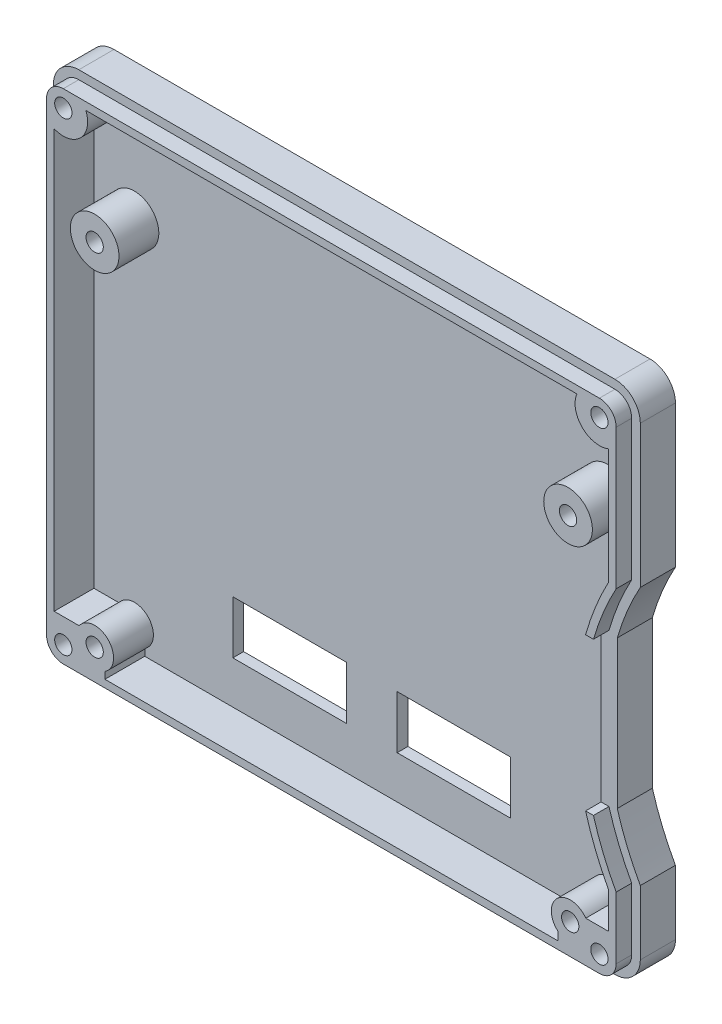
SolidWorks part; units mm, degrees
material "ABS"
ref_plane "Front Plane" through (0, 0, 0) normal (0, 0, 1) x (1, 0, 0)
ref_plane "Top Plane" through (0, 0, 0) normal (0, 1, 0) x (1, 0, 0)
ref_plane "Right Plane" through (0, 0, 0) normal (1, 0, 0) x (0, 0, -1)
sketch "Sketch1" plane through (0, 0, 0) normal (0, 0, 1) x (1, 0, 0)
  line L1 (-54.3, -47.7) -> (54.3, -47.7)
  line L2 (-54.3, -47.7) -> (-54.3, 47.7)
  line L3 (-54.3, 47.7) -> (54.3, 47.7)
  line L4 (54.3, -47.7) -> (54.3, 47.7)
  line L5 (-54.3, -47.7) -> (54.3, 47.7) construction
  line L6 (-54.3, 47.7) -> (54.3, -47.7) construction
  point P0 (0, 0)
  dimension "D1" = 108.6
  dimension "D2" = 95.4
extrude "Boss-Extrude1" add sketch "Sketch1" along normal blind 6.5
fillet "Fillet1" radius 4.7 4 edges at (-54.3, 47.7, 3.25) (-54.3, -47.7, 3.25) (54.3, -47.7, 3.25) (54.3, 47.7, 3.25)
sketch "Sketch4" plane through (0, 0, 6.5) normal (0, 0, 1) x (1, 0, 0)
  line L0 (54.3, -43) -> (54.3, 43) construction
  line L1 (-49.6, -47.7) -> (49.6, -47.7) construction
  line L2 (50.037, 6.4675) -> (50.037, -20.8702)
  arc A0 (50.037, -20.8702) -> (50.037, 6.4675) centre (97.196, -7.2014) ccw
  dimension "D1" = 98.2
  dimension "D2" = 42.896
  dimension "D3" = 40.4986
  dimension "D4" = 4.263
extrude "Cut-Extrude2" cut sketch "Sketch4" against normal through all
shell "Shell1" thickness 3 removed face at (17.3413, -2.4004, 6.5)
sketch "Sketch3" plane through (0, 0, 6.5) normal (0, 0, 1) x (1, 0, 0)
  line L0 (-49.6, -47.7) -> (49.6, -47.7) construction
  line L1 (-25.6, -27) -> (-4.6, -27)
  line L2 (-25.6, -27) -> (-25.6, -36.8)
  line L3 (-25.6, -36.8) -> (-4.6, -36.8)
  line L4 (-4.6, -27) -> (-4.6, -36.8)
  line L5 (4.8, -27) -> (25.8, -27)
  line L6 (4.8, -27) -> (4.8, -36.8)
  line L7 (4.8, -36.8) -> (25.8, -36.8)
  line L8 (25.8, -27) -> (25.8, -36.8)
  line L9 (-54.3, 43) -> (-54.3, -43) construction
  dimension "D1" = 21
  dimension "D2" = 9.4
  dimension "D3" = 9.8
  dimension "D4" = 10.9
  dimension "D5" = 28.7
extrude "Cut-Extrude1" cut sketch "Sketch3" against normal through all
sketch "Sketch5" plane through (0, 0, 6.5) normal (0, 0, 1) x (1, 0, 0)
  line L0 (-49.6, -47.7) -> (49.6, -47.7) construction
  line L1 (-54.3, 43) -> (-54.3, -43) construction
  line L2 (49.6, 47.7) -> (-49.6, 47.7) construction
  line L3 (54.3, 16.6888) -> (54.3, 43) construction
  line L4 (54.3, -43) -> (54.3, -31.0915) construction
  line L5 (-49.6, -47.7) -> (49.6, -47.7) construction
  line L6 (-54.3, 43) -> (-54.3, -43) construction
  line L7 (49.6, 47.7) -> (-49.6, 47.7) construction
  line L8 (54.3, 16.6888) -> (54.3, 43) construction
  line L9 (54.3, -43) -> (54.3, -31.0915) construction
  line L10 (52.7, 17.1008) -> (52.7, 43)
  line L11 (49.6, 46.1) -> (-49.6, 46.1)
  line L12 (-52.7, 43) -> (-52.7, -43)
  line L13 (-49.6, -46.1) -> (49.6, -46.1)
  line L14 (52.7, -43) -> (52.7, -31.5035)
  line L15 (-49.6, -44.7) -> (49.6, -44.7) construction
  line L16 (-51.3, 43) -> (-51.3, -43) construction
  line L17 (49.6, 44.7) -> (-49.6, 44.7) construction
  line L18 (51.3, 17.4556) -> (51.3, 43) construction
  line L19 (51.3, -43) -> (51.3, -31.8583) construction
  line L20 (-49.6, -44.7) -> (49.6, -44.7)
  line L21 (-51.3, 43) -> (-51.3, -43)
  line L22 (49.6, 44.7) -> (-49.6, 44.7)
  line L23 (51.3, 17.4556) -> (51.3, 43)
  line L24 (51.3, -43) -> (51.3, -31.8583)
  line L25 (48.5002, 6.9129) -> (47.0443, 6.9129)
  line L26 (48.5002, -21.3156) -> (47.0443, -21.3156)
  arc A0 (-54.3, -43) -> (-49.6, -47.7) centre (-49.6, -43) ccw construction
  arc A1 (-49.6, 47.7) -> (-54.3, 43) centre (-49.6, 43) ccw construction
  arc A2 (54.3, 43) -> (49.6, 47.7) centre (49.6, 43) ccw construction
  arc A3 (49.6, -47.7) -> (54.3, -43) centre (49.6, -43) ccw construction
  arc A4 (-54.3, -43) -> (-49.6, -47.7) centre (-49.6, -43) ccw construction
  arc A5 (-49.6, 47.7) -> (-54.3, 43) centre (-49.6, 43) ccw construction
  arc A6 (54.3, 43) -> (49.6, 47.7) centre (49.6, 43) ccw construction
  arc A7 (49.6, -47.7) -> (54.3, -43) centre (49.6, -43) ccw construction
  arc A8 (50.037, -20.8702) -> (54.3, -31.0915) centre (97.196, -7.2014) ccw construction
  arc A9 (50.037, -20.8702) -> (54.3, -31.0915) centre (97.196, -7.2014) ccw construction
  arc A10 (54.3, 16.6888) -> (50.037, 6.4675) centre (97.196, -7.2014) ccw construction
  arc A11 (54.3, 16.6888) -> (50.037, 6.4675) centre (97.196, -7.2014) ccw construction
  arc A12 (52.7, 17.1008) -> (48.5002, 6.9129) centre (97.196, -7.2014) ccw
  arc A13 (52.7, 43) -> (49.6, 46.1) centre (49.6, 43) ccw
  arc A14 (-49.6, 46.1) -> (-52.7, 43) centre (-49.6, 43) ccw
  arc A15 (-52.7, -43) -> (-49.6, -46.1) centre (-49.6, -43) ccw
  arc A16 (49.6, -46.1) -> (52.7, -43) centre (49.6, -43) ccw
  arc A17 (48.5002, -21.3156) -> (52.7, -31.5035) centre (97.196, -7.2014) ccw
  arc A18 (-51.3, -43) -> (-49.6, -44.7) centre (-49.6, -43) ccw construction
  arc A19 (-49.6, 44.7) -> (-51.3, 43) centre (-49.6, 43) ccw construction
  arc A20 (51.3, 43) -> (49.6, 44.7) centre (49.6, 43) ccw construction
  arc A21 (49.6, -44.7) -> (51.3, -43) centre (49.6, -43) ccw construction
  arc A22 (-51.3, -43) -> (-49.6, -44.7) centre (-49.6, -43) ccw
  arc A23 (-49.6, 44.7) -> (-51.3, 43) centre (-49.6, 43) ccw
  arc A24 (51.3, 43) -> (49.6, 44.7) centre (49.6, 43) ccw
  arc A25 (49.6, -44.7) -> (51.3, -43) centre (49.6, -43) ccw
  arc A26 (47.037, -21.2897) -> (51.3, -31.8583) centre (97.196, -7.2014) ccw construction
  arc A27 (47.0443, -21.3156) -> (51.3, -31.8583) centre (97.196, -7.2014) ccw
  arc A28 (51.3, 17.4556) -> (47.037, 6.887) centre (97.196, -7.2014) ccw construction
  arc A29 (51.3, 17.4556) -> (47.0443, 6.9129) centre (97.196, -7.2014) ccw
  dimension "D1" = 1.6
extrude "Boss-Extrude2" add sketch "Sketch5" along normal blind 2.87
sketch "Sketch6" plane through (0, 0, 2) normal (0, 0, 1) x (1, 0, 0)
  line L0 (-54.3, 43) -> (-54.3, -43) construction
  line L1 (49.6, 47.7) -> (-49.6, 47.7) construction
  line L2 (-49.6, -47.7) -> (49.6, -47.7) construction
  line L3 (54.3, -43) -> (54.3, -31.0915) construction
  circle A0 centre (-49.6, 43) radius 1.6
  circle A1 centre (-43.8, 24.4) radius 1.6
  circle A2 centre (43.8, 24.4) radius 1.6
  circle A3 centre (49.6, 43) radius 1.6
  circle A4 centre (49.6, -43) radius 1.6
  circle A5 centre (44.2, -40.5) radius 1.6
  circle A6 centre (-49.6, -43) radius 1.6
  circle A7 centre (-43.8, -40.5) radius 1.6
  dimension "D1" = 3.2
  dimension "D2" = 4.7
  dimension "D3" = 4.7
  dimension "D4" = 4.7
  dimension "D5" = 4.7
  dimension "D6" = 87.6
  dimension "D7" = 18.6
  dimension "D8" = 5.8
  dimension "D9" = 64.9
  dimension "D10" = 88
extrude "Cut-Extrude3" cut sketch "Sketch6" against normal through all and the other way through all
sketch "Sketch7" plane through (0, 0, 2) normal (0, 0, 1) x (1, 0, 0)
  line L0 (47.0723, -38.5) -> (51.3, -38.5)
  line L1 (41.9, -43.1382) -> (41.9, -44.7)
  line L2 (-49.6, -44.7) -> (49.6, -44.7) construction
  line L3 (51.3, -43) -> (51.3, -31.8583) construction
  line L4 (-49.6, -44.7) -> (-41.9, -44.7)
  line L5 (51.3, -43) -> (51.3, -38.5)
  line L6 (41.9, -44.7) -> (49.6, -44.7)
  line L7 (54.3, -43) -> (54.3, -31.0915) construction
  line L8 (-49.6, -47.7) -> (49.6, -47.7) construction
  line L9 (-51.3, -43) -> (-51.3, 43) construction
  line L10 (-49.6, 44.7) -> (49.6, 44.7) construction
  line L11 (-51.3, -43) -> (-51.3, -38.5)
  line L12 (-49.6, 44.7) -> (-45.4335, 44.7)
  line L13 (-51.3, 38.8335) -> (-51.3, 43)
  line L14 (45.4335, 44.7) -> (49.6, 44.7)
  line L15 (51.3, 43) -> (51.3, 17.4556) construction
  line L16 (51.3, 43) -> (51.3, 38.8335)
  line L17 (-51.3, -38.5) -> (-46.6723, -38.5)
  line L18 (-41.9, -44.7) -> (-41.9, -43.4394)
  line L19 (-54.3, 43) -> (-54.3, -43) construction
  circle A0 centre (-43.8, 24.4) radius 4.5
  circle A1 centre (43.8, 24.4) radius 4.5
  arc A2 (-51.3, 38.8335) -> (-45.4335, 44.7) centre (-49.6, 43) ccw
  arc A3 (45.4335, 44.7) -> (51.3, 38.8335) centre (49.6, 43) ccw
  arc A4 (-51.3, -43) -> (-49.6, -44.7) centre (-49.6, -43) ccw construction
  arc A5 (-49.6, 44.7) -> (-51.3, 43) centre (-49.6, 43) ccw construction
  arc A6 (47.0723, -38.5) -> (41.9, -43.1382) centre (44.2, -40.5) ccw
  arc A8 (49.6, -44.7) -> (51.3, -43) centre (49.6, -43) ccw construction
  arc A9 (49.6, -44.7) -> (51.3, -43) centre (49.6, -43) ccw
  arc A10 (-49.6, 44.7) -> (-51.3, 43) centre (-49.6, 43) ccw
  arc A11 (51.3, 43) -> (49.6, 44.7) centre (49.6, 43) ccw construction
  arc A12 (51.3, 43) -> (49.6, 44.7) centre (49.6, 43) ccw
  arc A13 (-41.9, -43.4394) -> (-46.6723, -38.5) centre (-43.8, -40.5) ccw
  arc A14 (-51.3, -43) -> (-49.6, -44.7) centre (-49.6, -43) ccw
  circle A15 centre (-43.8, -40.5) radius 1.6 construction
  circle A16 centre (-43.8, -40.5) radius 1.6
  circle A17 centre (-43.8, 24.4) radius 1.6 construction
  circle A18 centre (-49.6, 43) radius 1.6 construction
  circle A19 centre (-43.8, 24.4) radius 1.6
  circle A20 centre (-49.6, 43) radius 1.6
  circle A21 centre (49.6, 43) radius 1.6 construction
  circle A22 centre (43.8, 24.4) radius 1.6 construction
  circle A23 centre (44.2, -40.5) radius 1.6 construction
  circle A24 centre (49.6, 43) radius 1.6
  circle A25 centre (43.8, 24.4) radius 1.6
  circle A26 centre (44.2, -40.5) radius 1.6
  dimension "D3" = 3.5
  dimension "D4" = 9
  dimension "D1" = 12.4
  dimension "D2" = 9.2
  dimension "D5" = 12.4
extrude "Boss-Extrude3" add sketch "Sketch7" along normal up to surface (7.37 mm away) up to face at (16.5815, -2.4004, 9.37)
sketch "Sketch8" plane through (0, 0, 0) normal (0, 0, -1) x (-1, 0, 0)
  circle A1 centre (-49.6, -43) radius 1.6
  circle A2 centre (-49.6, -43) radius 1.6
  circle A3 centre (49.6, -43) radius 1.6
  circle A4 centre (49.6, -43) radius 1.6
  dimension "D1" = 0
  dimension "D2" = 0
extrude "Cut-Extrude4" cut sketch "Sketch8" against normal through all
sketch "Sketch9" plane through (0, 0, 0) normal (0, 0, -1) x (-1, 0, 0)
  circle A0 centre (-49.6, -43) radius 2.9
  circle A1 centre (-49.6, 43) radius 2.9
  circle A2 centre (49.6, 43) radius 2.9
  circle A3 centre (49.6, -43) radius 2.9
  dimension "D1" = 5.8
extrude "Cut-Extrude5" cut sketch "Sketch9" against normal blind 6
